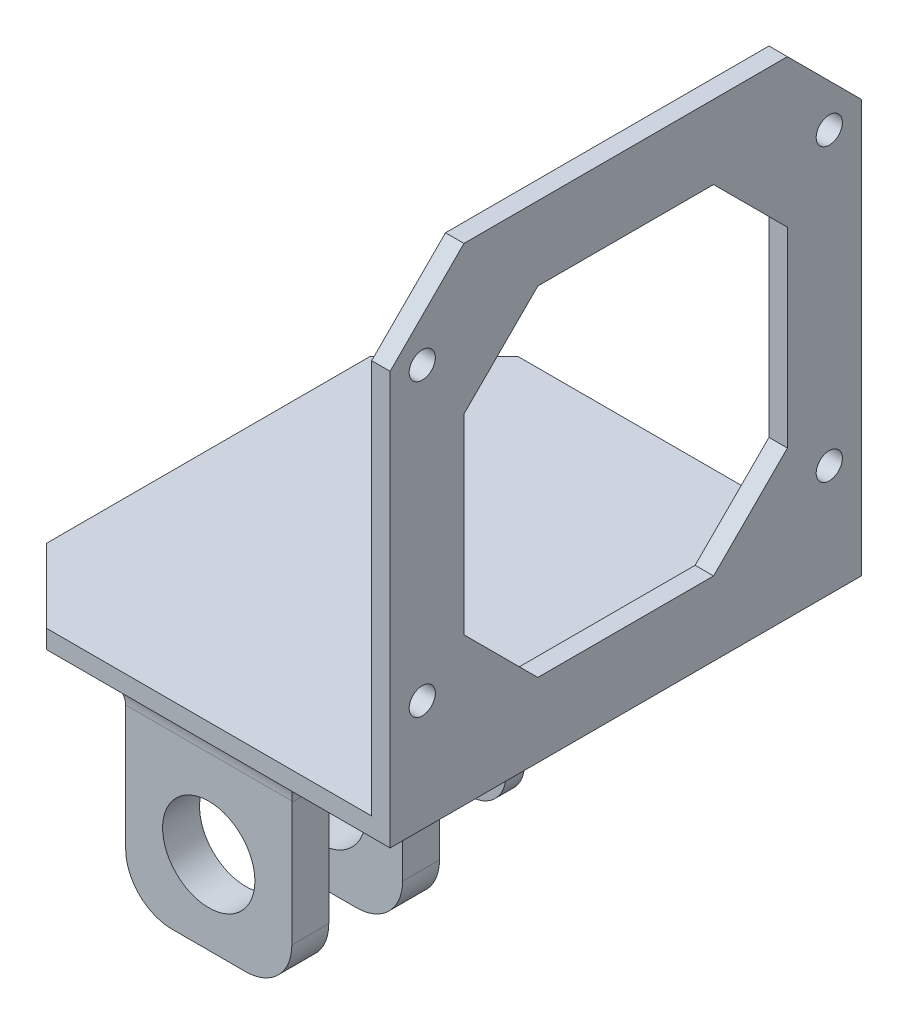
SolidWorks part; units mm, degrees
material "ABS PC"
ref_plane "Front Plane" through (0, 0, 0) normal (0, 0, 1) x (1, 0, 0)
ref_plane "Top Plane" through (0, 0, 0) normal (0, 1, 0) x (1, 0, 0)
ref_plane "Right Plane" through (0, 0, 0) normal (1, 0, 0) x (0, 0, -1)
sketch "Sketch1" plane through (0, 0, 0) normal (0, 1, 0) x (1, 0, 0)
  line L0 (0, 40.513) -> (71.755, 40.513) construction
  line L1 (0, 0) -> (71.755, 0)
  line L2 (0, 0) -> (0, 81.026)
  line L3 (0, 81.026) -> (71.755, 81.026)
  line L4 (71.755, 0) -> (71.755, 81.026)
  line L5 (35.8775, 81.026) -> (35.8775, 0) construction
  dimension "D1" = 71.755
  dimension "D2" = 81.026
extrude "Boss-Extrude1" add sketch "Sketch1" along normal blind 3.175
ref_plane "Plane2" through (0, 0, -40.513) normal (0, 0, -1) x (-1, 0, 0)
ref_plane "Plane1" through (35.8775, 0, 0) normal (1, 0, 0) x (0, 0, -1)
sketch "Sketch3" plane through (0, 3.175, 0) normal (0, 1, 0) x (1, 0, 0)
  line L0 (71.755, 0) -> (68.58, 0)
  line L1 (0, 0) -> (71.755, 0) construction
  line L2 (68.58, 0) -> (68.58, 81.026)
  line L3 (71.755, 81.026) -> (0, 81.026) construction
  line L4 (68.58, 81.026) -> (71.755, 81.026)
  line L5 (71.755, 81.026) -> (71.755, 0)
  dimension "D1" = 3.175
extrude "Boss-Extrude4" add sketch "Sketch3" along normal blind 80.518
sketch "Sketch8" plane through (0, 0, -40.513) normal (0, 0, 1) x (1, 0, 0)
  line L0 (26.3525, 0) -> (26.3525, -31.75)
  line L1 (0, 0) -> (71.755, 0) construction
  line L2 (45.4025, 0) -> (45.4025, -31.75)
  line L3 (45.4025, -31.75) -> (26.3525, -31.75)
  line L4 (26.3525, 0) -> (45.4025, 0)
  line L5 (35.8775, -44.5643) -> (35.8775, 44.5643) construction
  circle A1 centre (35.8775, -21.25) radius 3.175
  point P8 (35.8775, 0)
  dimension "D3" = 10.5
  dimension "D4" = 6.35
  dimension "D1" = 19.05
  dimension "D2" = 31.75
extrude "Boss-Extrude10" add sketch "Sketch8" along normal mid plane 3.175 from offset 7.366 contours L4 L2 L3 L0 | A1 offset against normal yes
fillet "Fillet1" radius 6.35 2 edges at (45.4025, -31.75, -47.879) (26.3525, -31.75, -47.879)
fillet "Fillet2" radius 8.4667 4 edges at (45.4025, 0, -47.879) (35.8775, 0, -46.2915) (26.3525, 0, -47.879) (35.8775, 0, -49.4665)
sketch "Sketch9" plane through (71.755, 0, 0) normal (1, 0, 0) x (0, 0, -1)
  line L0 (0, 83.693) -> (81.026, 0) construction
  line L1 (81.026, 83.693) -> (81.026, 0) construction
  line L2 (12.7, 12.7) -> (68.326, 12.7)
  line L3 (12.7, 12.7) -> (12.7, 70.993)
  line L4 (12.7, 70.993) -> (68.326, 70.993)
  line L5 (68.326, 12.7) -> (68.326, 70.993)
  line L6 (12.7, 12.7) -> (68.326, 70.993) construction
  line L7 (12.7, 70.993) -> (68.326, 12.7) construction
  line L8 (0, 83.693) -> (81.026, 83.693) construction
  point P4 (40.513, 41.8465)
  dimension "D1" = 12.7
  dimension "D2" = 12.7
extrude "Cut-Extrude1" cut sketch "Sketch9" against normal up to next contours L3 L2 L5 L4
fillet "Fillet3" radius 12.7 4 edges at (70.1675, 83.693, 0) (0, 1.5875, 0) (70.1675, 83.693, -81.026) (0, 1.5875, -81.026) profile chamfer
chamfer "Chamfer1" distance 12.7 angle 45 4 edges at (70.1675, 12.7, -12.7) (70.1675, 12.7, -68.326) (70.1675, 70.993, -68.326) (70.1675, 70.993, -12.7)
sketch "Sketch10" plane through (0, 0, 0) normal (0, 0, 1) x (1, 0, 0)
  line L0 (35.8775, -21.25) -> (35.8775, 0)
  line L1 (17.8858, 0) -> (53.8692, 0) construction
  line L2 (21.59, 0) -> (21.59, -35.5375)
  line L3 (12.7, 0) -> (71.755, 0) construction
  line L4 (21.59, -35.5375) -> (50.165, -35.5375)
  line L5 (50.165, -35.5375) -> (50.165, 0)
  line L6 (21.59, 0) -> (50.165, 0)
  circle A0 centre (35.8775, -21.25) radius 7.9375
  dimension "D1" = 15.875
  dimension "D2" = 14.2875
  dimension "D3" = 28.575
  dimension "D4" = 14.2875
extrude "Boss-Extrude11" add sketch "Sketch10" along normal blind 6.35 from offset 11.0376 offset against normal yes
pattern_linear "LPattern1" count 2 spacing 19.05 along (0, 0, -1) of "Boss-Extrude11"
fillet "Fillet4" radius 6.35 8 edges at (50.165, 0, -26.9126) (50.165, 0, -7.8626) (35.8775, 0, -4.6876) (21.59, 0, -7.8626) (35.8775, 0, -11.0376) (35.8775, 0, -23.7376) (21.59, 0, -26.9126) (35.8775, 0, -30.0876)
fillet "Fillet5" radius 7.9375 4 edges at (50.165, -35.5375, -26.9126) (50.165, -35.5375, -7.8626) (21.59, -35.5375, -7.8626) (21.59, -35.5375, -26.9126)
sketch "Sketch13" plane through (71.755, 0, 0) normal (1, 0, 0) x (0, 0, -1)
  circle A0 centre (75.526, 69.175) radius 2.25
  circle A1 centre (5.526, 69.175) radius 2.25
  circle A2 centre (5.526, 19.175) radius 2.25
  circle A3 centre (75.526, 19.175) radius 2.25
  dimension "D1" = 4.5
extrude "Cut-Extrude2" cut sketch "Sketch13" against normal up to next
